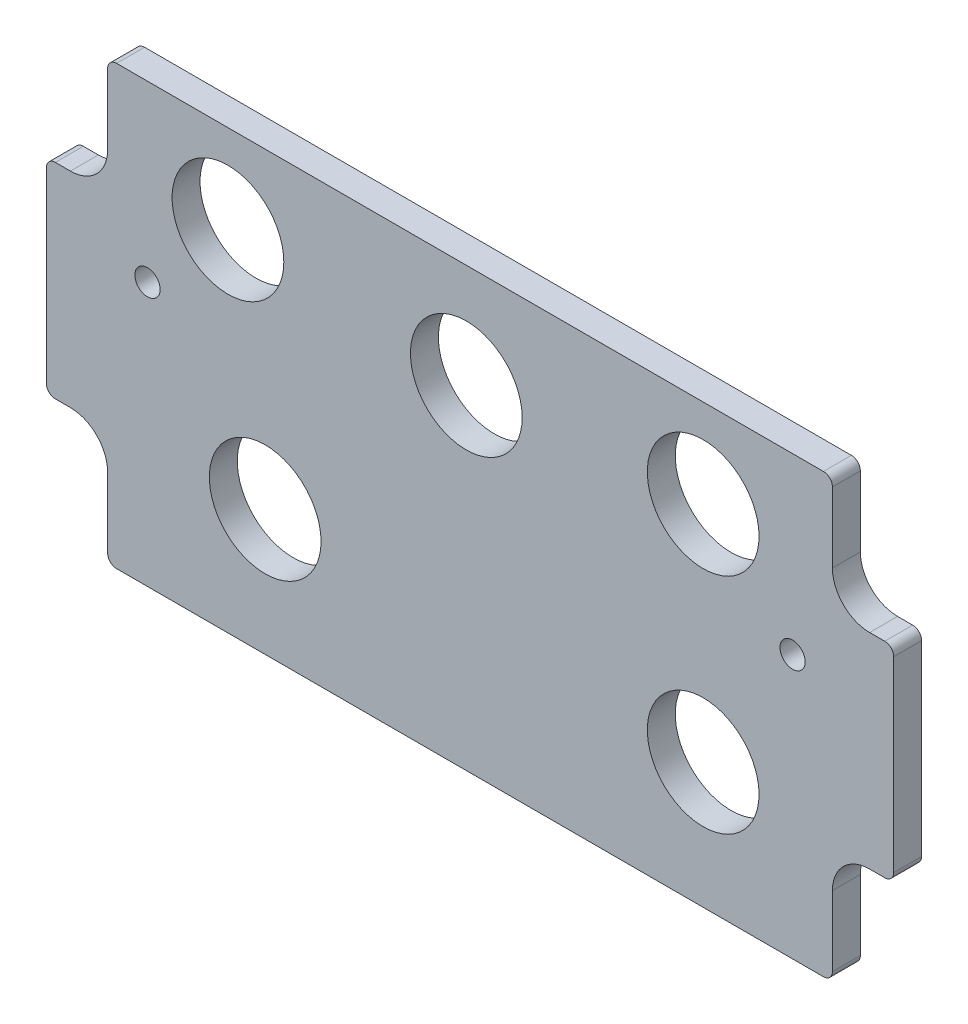
SolidWorks part; units mm, degrees
ref_plane "Front Plane" through (0, 0, 0) normal (0, 0, 1) x (1, 0, 0)
ref_plane "Top Plane" through (0, 0, 0) normal (0, 1, 0) x (1, 0, 0)
ref_plane "Right Plane" through (0, 0, 0) normal (1, 0, 0) x (0, 0, -1)
sketch "Sketch1" plane through (0, 0, 0) normal (0, 0, 1) x (1, 0, 0)
  line L12 (134.8105, 61.9125) -> (134.8105, 73.8822)
  line L13 (133.2865, 75.4062) -> (12.7635, 75.4062)
  line L14 (11.2395, 73.8822) -> (11.2395, 61.9125)
  line L15 (4.8895, 55.5625) -> (2.3178, 55.5625)
  line L16 (0.7938, 54.0385) -> (0.7938, 22.1615)
  line L17 (2.3178, 20.6375) -> (4.8895, 20.6375)
  line L18 (11.2395, 14.2875) -> (11.2395, 2.3178)
  line L19 (12.7635, 0.7938) -> (133.2865, 0.7937)
  line L20 (134.8105, 2.3177) -> (134.8105, 14.2875)
  line L21 (141.1605, 20.6375) -> (143.7323, 20.6375)
  line L22 (145.2563, 22.1615) -> (145.2563, 54.0385)
  line L23 (143.7323, 55.5625) -> (141.1605, 55.5625)
  line L24 (134.8105, 61.9125) -> (134.8105, 73.8822)
  line L25 (133.2865, 75.4062) -> (12.7635, 75.4062)
  line L26 (11.2395, 73.8822) -> (11.2395, 61.9125)
  line L27 (4.8895, 55.5625) -> (2.3178, 55.5625)
  line L28 (0.7938, 54.0385) -> (0.7938, 22.1615)
  line L29 (2.3178, 20.6375) -> (4.8895, 20.6375)
  line L30 (11.2395, 14.2875) -> (11.2395, 2.3178)
  line L31 (12.7635, 0.7938) -> (133.2865, 0.7937)
  line L32 (134.8105, 2.3177) -> (134.8105, 14.2875)
  line L33 (141.1605, 20.6375) -> (143.7323, 20.6375)
  line L34 (145.2563, 22.1615) -> (145.2563, 54.0385)
  line L35 (143.7323, 55.5625) -> (141.1605, 55.5625)
  arc A12 (134.8105, 61.9125) -> (141.1605, 55.5625) centre (141.1605, 61.9125) ccw
  arc A13 (134.8105, 73.8822) -> (133.2865, 75.4062) centre (133.2865, 73.8822) ccw
  arc A14 (12.7635, 75.4062) -> (11.2395, 73.8822) centre (12.7635, 73.8822) ccw
  arc A15 (4.8895, 55.5625) -> (11.2395, 61.9125) centre (4.8895, 61.9125) ccw
  arc A16 (2.3178, 55.5625) -> (0.7938, 54.0385) centre (2.3178, 54.0385) ccw
  arc A17 (0.7938, 22.1615) -> (2.3178, 20.6375) centre (2.3178, 22.1615) ccw
  arc A18 (11.2395, 14.2875) -> (4.8895, 20.6375) centre (4.8895, 14.2875) ccw
  arc A19 (11.2395, 2.3178) -> (12.7635, 0.7938) centre (12.7635, 2.3178) ccw
  arc A20 (133.2865, 0.7937) -> (134.8105, 2.3177) centre (133.2865, 2.3177) ccw
  arc A21 (141.1605, 20.6375) -> (134.8105, 14.2875) centre (141.1605, 14.2875) ccw
  arc A22 (143.7323, 20.6375) -> (145.2563, 22.1615) centre (143.7323, 22.1615) ccw
  arc A23 (145.2563, 54.0385) -> (143.7323, 55.5625) centre (143.7323, 54.0385) ccw
  arc A24 (134.8105, 61.9125) -> (141.1605, 55.5625) centre (141.1605, 61.9125) ccw
  arc A25 (134.8105, 73.8822) -> (133.2865, 75.4062) centre (133.2865, 73.8822) ccw
  arc A26 (12.7635, 75.4062) -> (11.2395, 73.8822) centre (12.7635, 73.8822) ccw
  arc A27 (4.8895, 55.5625) -> (11.2395, 61.9125) centre (4.8895, 61.9125) ccw
  arc A28 (2.3178, 55.5625) -> (0.7938, 54.0385) centre (2.3178, 54.0385) ccw
  arc A29 (0.7938, 22.1615) -> (2.3178, 20.6375) centre (2.3178, 22.1615) ccw
  arc A30 (11.2395, 14.2875) -> (4.8895, 20.6375) centre (4.8895, 14.2875) ccw
  arc A31 (11.2395, 2.3178) -> (12.7635, 0.7938) centre (12.7635, 2.3178) ccw
  arc A32 (133.2865, 0.7937) -> (134.8105, 2.3177) centre (133.2865, 2.3177) ccw
  arc A33 (141.1605, 20.6375) -> (134.8105, 14.2875) centre (141.1605, 14.2875) ccw
  arc A34 (143.7323, 20.6375) -> (145.2563, 22.1615) centre (143.7323, 22.1615) ccw
  arc A35 (145.2563, 54.0385) -> (143.7323, 55.5625) centre (143.7323, 54.0385) ccw
  dimension "D1" = 0
extrude "Boss-Extrude1" add sketch "Sketch1" along normal blind 4.7625
hole_wizard "3/4 (0.75) Diameter Hole1" positions "Sketch3" profile "Sketch2" hole size "3/4" standard "ANSI Inch" end condition through all
sketch "Sketch3" plane through (0, 0, 4.7625) normal (0, 0, 1) x (1, 0, 0)
  point P0 (31.75, 60.325)
  point P4 (72.39, 57.658)
  point P7 (112.776, 60.325)
  point P10 (112.776, 22.225)
  point P13 (38.1, 22.225)
sketch "Sketch2" plane through (31.75, 60.325, 4.7625) normal (1, 0, 0) x (0, -1, 0)
  line L0 (0, 0) -> (0, 4.7625)
  line L1 (0, 4.7625) -> (9.525, 4.7625)
  line L2 (9.525, 4.7625) -> (9.525, 0)
  line L5 (9.525, 0) -> (0, 0)
  line L11 (0, -6.35) -> (0, 107.95) construction
  dimension "Thru Hole Dia." = 19.05
  dimension "Thru Hole Depth" = 4.7625
hole_wizard "#6 Clearance Hole1" positions "Sketch5" profile "Sketch4" hole size "#6" standard "ANSI Inch" end condition through all
sketch "Sketch5" plane through (0, 0, 4.7625) normal (0, 0, 1) x (1, 0, 0)
  point P0 (18.034, 45.72)
  point P3 (128.016, 45.72)
sketch "Sketch4" plane through (18.034, 45.72, 4.7625) normal (1, 0, 0) x (0, -1, 0)
  line L0 (0, 0) -> (0, 4.7625)
  line L1 (0, 4.7625) -> (2.1526, 4.7625)
  line L2 (2.1526, 4.7625) -> (2.1526, 0)
  line L5 (2.1526, 0) -> (0, 0)
  line L11 (0, -6.35) -> (0, 107.95) construction
  dimension "Thru Hole Dia." = 4.3053
  dimension "Thru Hole Depth" = 4.7625
